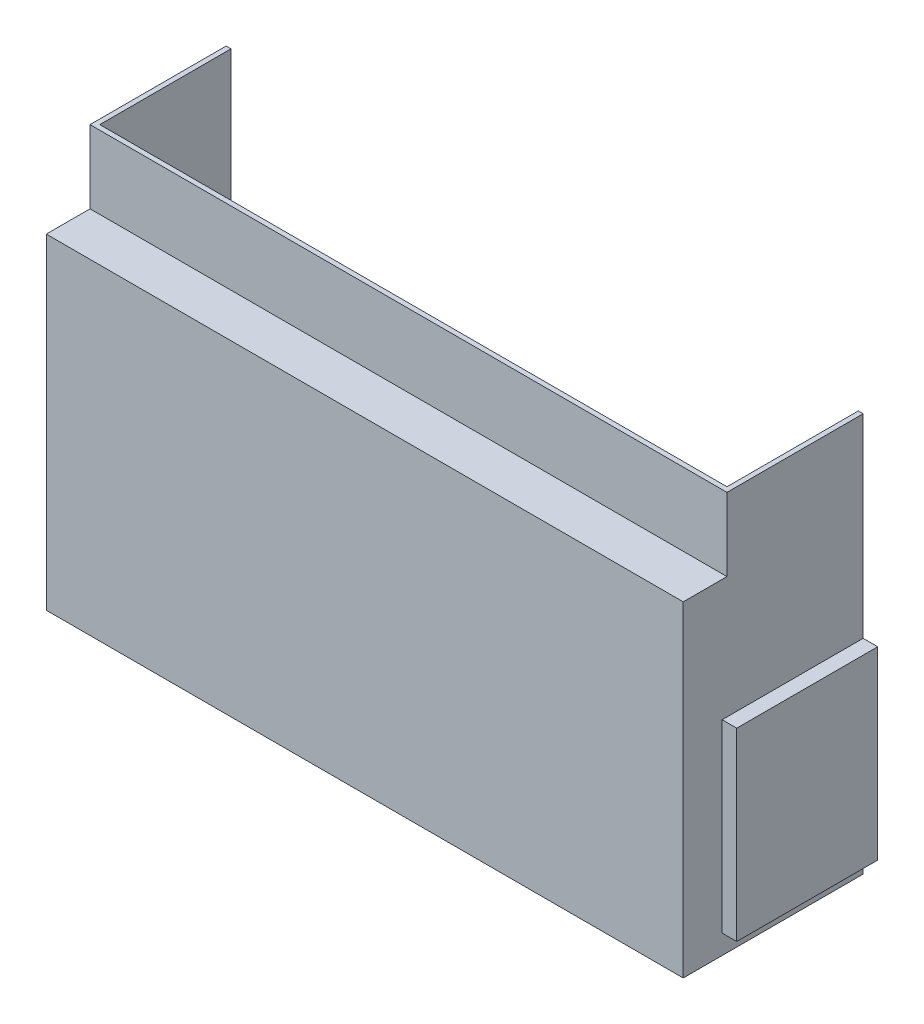
SolidWorks part; units mm, degrees
ref_plane "Front Plane" through (0, 0, 0) normal (0, 0, 1) x (1, 0, 0)
ref_plane "Top Plane" through (0, 0, 0) normal (0, 1, 0) x (1, 0, 0)
ref_plane "Right Plane" through (0, 0, 0) normal (1, 0, 0) x (0, 0, -1)
sketch "Sketch1" plane through (0, 0, 0) normal (0, 0, 1) x (1, 0, 0)
  line L1 (-187.443, 106.0113) -> (222.132, 106.0113)
  line L2 (-187.443, 106.0113) -> (-187.443, -151.1637)
  line L3 (-187.443, -151.1637) -> (222.132, -151.1637)
  line L4 (222.132, 106.0113) -> (222.132, -151.1637)
  dimension "D1" = 409.575
  dimension "D2" = 257.175
extrude "Cover Body" add sketch "Sketch1" along normal blind 98.425
ref_plane "Mirror Plane" through (17.3445, 0, 0) normal (-1, 0, 0) x (0, 0, 1)
sketch "Sketch2" plane through (-187.443, 0, 0) normal (1, 0, 0) x (0, 0, -1)
  line L0 (-98.425, 106.0113) -> (0, 106.0113) construction
  line L1 (-54.102, 83.9133) -> (0, 83.9133)
  line L2 (-54.102, 83.9133) -> (-54.102, 4.4113)
  line L3 (-54.102, 4.4113) -> (0, 4.4113)
  line L4 (0, 83.9133) -> (0, 4.4113)
  line L5 (0, -151.1637) -> (0, 106.0113) construction
  dimension "D1" = 79.502
  dimension "D2" = 54.102
  dimension "D3" = 22.098
sketch "Sketch5" plane through (222.132, 0, 0) normal (1, 0, 0) x (0, 0, -1)
  line L0 (0, -151.1637) -> (0, 106.0113) construction
  line L1 (0, -138.4637) -> (-73.025, -138.4637)
  line L2 (0, -138.4637) -> (0, -24.1637)
  line L3 (0, -24.1637) -> (-73.025, -24.1637)
  line L4 (-73.025, -138.4637) -> (-73.025, -24.1637)
  line L6 (-98.425, 106.0113) -> (0, 106.0113) construction
  dimension "D1" = 114.3
  dimension "D2" = 73.025
  dimension "D3" = 244.475
extrude "IGBT Extrusion" add sketch "Sketch5" along normal blind 9.525
sketch "Sketch4" [suppressed] plane through (220.5445, 0, 0) normal (1, 0, 0) x (0, 0, -1)
  line L1 (0, -151.1637) -> (-6.35, -151.1637)
  line L2 (0, -151.1637) -> (0, -138.4637)
  line L3 (0, -138.4637) -> (-6.35, -138.4637)
  line L4 (-6.35, -151.1637) -> (-6.35, -138.4637)
  dimension "D1" = 6.35
  dimension "D2" = 12.7
sketch "Sketch8" plane through (0, 106.0113, 0) normal (0, 1, 0) x (1, 0, 0)
  line L0 (-187.443, -69.85) -> (-111.243, -69.85)
  line L4 (222.132, -69.85) -> (145.932, -69.85)
  line L5 (222.132, -98.425) -> (222.132, 0) construction
  line L6 (222.132, -69.85) -> (385.3569, -82.616)
  line L7 (385.3569, -82.616) -> (373.1862, -238.2293)
  line L8 (373.1862, -238.2293) -> (-256.5101, -238.2293)
  line L9 (-256.5101, -238.2293) -> (-256.5101, -69.85)
  line L10 (-256.5101, -69.85) -> (-187.443, -69.85)
  line L12 (-187.443, -98.425) -> (-187.443, 0) construction
  line L13 (222.132, 0) -> (-187.443, 0) construction
  line L14 (-111.243, -69.85) -> (145.932, -69.85)
  dimension "D2" = 69.85
  dimension "D4" = 69.85
extrude "Cut-Extrude1" cut sketch "Sketch8" against normal blind 50.8
shell "Shell" thickness 3.175 removed face at (123.3101, -60.8747, 0) removed face at (17.3445, 106.0113, 34.925) outward yes
sketch "Sketch10" plane through (0, 0, 0) normal (0, 0, -1) x (-1, 0, 0)
  line L16 (190.618, 106.0113) -> (187.443, 106.0113)
  line L17 (187.443, 106.0113) -> (187.443, -151.1637)
  line L18 (187.443, -151.1637) -> (-222.132, -151.1637)
  line L19 (-222.132, -151.1637) -> (-222.132, -138.4637)
  line L20 (-222.132, -138.4637) -> (-231.657, -138.4637)
  line L21 (-231.657, -138.4637) -> (-231.657, -24.1637)
  line L22 (-231.657, -24.1637) -> (-222.132, -24.1637)
  line L23 (-222.132, -138.4637) -> (-231.657, -138.4637)
  line L24 (-222.132, 106.0113) -> (-225.307, 106.0113)
  line L25 (-225.307, 106.0113) -> (-225.307, -20.9887)
  line L26 (-225.307, -20.9887) -> (-234.832, -20.9887)
  line L27 (-234.832, -20.9887) -> (-234.832, -141.6387)
  line L28 (-234.832, -141.6387) -> (-225.307, -141.6387)
  line L29 (-222.132, -24.1637) -> (-222.132, 106.0113)
  line L30 (-222.132, -24.1637) -> (-222.132, 106.0113)
  line L31 (190.618, -154.3387) -> (190.618, 106.0113)
  line L32 (190.618, 106.0113) -> (187.443, 106.0113)
  line L33 (187.443, 106.0113) -> (187.443, -151.1637)
  line L34 (187.443, -151.1637) -> (-222.132, -151.1637)
  line L35 (-222.132, -151.1637) -> (-222.132, -138.4637)
  line L36 (-225.307, -141.6387) -> (-225.307, -154.3387)
  line L37 (-231.657, -138.4637) -> (-231.657, -24.1637)
  line L38 (-231.657, -24.1637) -> (-222.132, -24.1637)
  line L39 (-225.307, -141.6387) -> (-225.307, -154.3387)
  line L40 (-222.132, 106.0113) -> (-225.307, 106.0113)
  line L41 (-225.307, 106.0113) -> (-225.307, -20.9887)
  line L42 (-225.307, -20.9887) -> (-234.832, -20.9887)
  line L43 (-234.832, -20.9887) -> (-234.832, -141.6387)
  line L44 (-234.832, -141.6387) -> (-225.307, -141.6387)
  line L45 (-225.307, -154.3387) -> (190.618, -154.3387)
  line L46 (-225.307, -154.3387) -> (190.618, -154.3387)
  line L47 (190.618, -154.3387) -> (190.618, 106.0113)
  dimension "D1" = 0
extrude "Boss-Extrude1" add sketch "Sketch10" along normal blind 15.875
